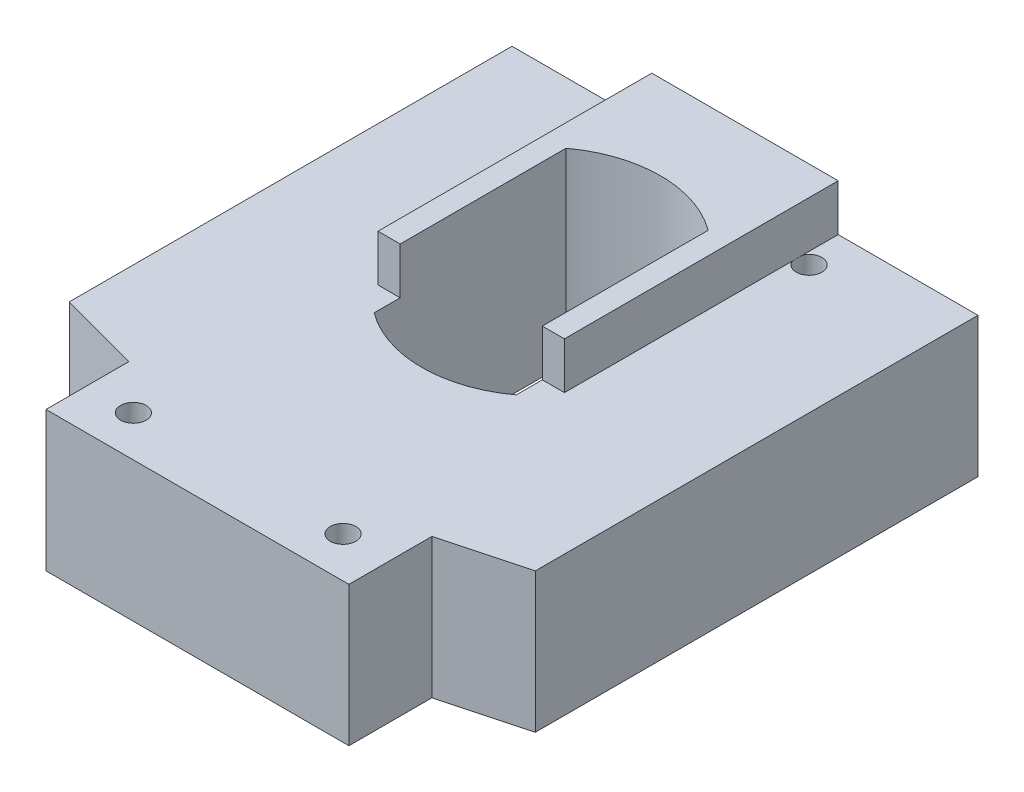
SolidWorks part; units mm, degrees
ref_plane "Front Plane" through (0, 0, 0) normal (0, 0, 1) x (1, 0, 0)
ref_plane "Top Plane" through (0, 0, 0) normal (0, 1, 0) x (1, 0, 0)
ref_plane "Right Plane" through (0, 0, 0) normal (1, 0, 0) x (0, 0, -1)
sketch "Sketch1" plane through (0, 0, 0) normal (0, 1, 0) x (1, 0, 0)
  line L0 (13, 23.5) -> (20, 23.5)
  line L1 (-9, -20) -> (9, -20) construction
  line L2 (-9, -20) -> (-9, 20) construction
  line L3 (-9, 20) -> (9, 20) construction
  line L4 (9, -20) -> (9, 20) construction
  line L5 (0, 20) -> (0, -20) construction
  line L6 (-9, 0) -> (9, 0) construction
  line L7 (-13, 23.5) -> (13, 23.5)
  line L8 (-13, 23.5) -> (-13, -23.5)
  line L9 (-13, -23.5) -> (13, -23.5)
  line L10 (13, 23.5) -> (13, -23.5)
  line L11 (0, -23.5) -> (0, 23.5) construction
  line L12 (-13, 0) -> (13, 0) construction
  line L13 (20, 23.5) -> (20, -14.5)
  line L14 (20, -14.5) -> (13, -16.3756)
  line L15 (-20, -14.5) -> (-13, -16.3756)
  line L16 (-20, 23.5) -> (-20, -14.5)
  line L17 (-13, 23.5) -> (-20, 23.5)
  circle A0 centre (-9, 20) radius 1.1
  circle A1 centre (9, 20) radius 1.1
  circle A2 centre (-9, -20) radius 1.1
  circle A3 centre (9, -20) radius 1.1
  point P0 (0, 0)
  point P8 (0, 0)
  point P18 (13, -16.7511)
  dimension "D3" = 2.2
  dimension "D1" = 18
  dimension "D2" = 40
  dimension "D4" = 26
  dimension "D5" = 47
  dimension "D6" = 38
  dimension "D7" = 40
  dimension "D8" = 75
extrude "Boss-Extrude1" add sketch "Sketch1" against normal blind 12 contours L8 L17 L16 L15 | L10 L7 L8 L9 A3 A2 A1 A0 | L14 L13 L0 L10 region at (0, 0, 0) region at (16.4719, 0, -4.0273) region at (-16.4719, 0, -4.0273)
sketch "Sketch2" plane through (0, 0, 0) normal (0, 0, 1) x (1, 0, 0)
  line L0 (0, -1000) -> (0, 49000) construction
  line L1 (-13, 0) -> (13, 0) construction
  line L2 (-8, 0) -> (-8, 4)
  line L3 (8, 0) -> (8, 4)
  line L4 (-8, 4) -> (8, 4)
  line L5 (-13, 0) -> (13, 0)
  circle A0 centre (-7, -4) radius 1.65
  circle A1 centre (7, -4) radius 1.65
  dimension "D1" = 3.3
  dimension "D2" = 14
  dimension "D3" = 4
  dimension "D4" = 16
  dimension "D5" = 4
extrude "Cut-Extrude1" [suppressed] cut sketch "Sketch2" against normal through all both and the other way through all contours A0 | A1
extrude "Boss-Extrude2" add sketch "Sketch2<3>" against normal up to surface (23.5 mm away) contours L0 L5 L3 L4 | L5 L0 L4 L2 region at (-4, 2, 0) region at (4, 2, 0) up to face at (0, -6, -23.5)
sketch "Sketch2<3>" plane through (0, 0, 0) normal (0, 0, 1) x (1, 0, 0) same geometry as "Sketch2"
sketch "Sketch3" plane through (0, 0, 0) normal (0, 1, 0) x (1, 0, 0)
  line L0 (20, 23.5) -> (-20, 23.5) construction
  line L1 (20, 23.5) -> (-20, 23.5) construction
  line L2 (0, -1000) -> (0, 49000) construction
  line L3 (-8, 0) -> (8, 0) construction
  line L4 (-1000, 6) -> (49000, 6) construction
  line L5 (-6.1, 14.2373) -> (-6.1, -2.2373)
  line L6 (6.1, 14.2373) -> (6.1, -2.2373)
  circle A0 centre (0, 6) radius 10.25
  point P10 (0, 0)
  dimension "D1" = 20.5
  dimension "D2" = 17.5
  dimension "D3" = 12.2
extrude "Cut-Extrude3" cut sketch "Sketch3" against normal through all both and the other way through all contours L6 A0 L5 region at (0, 0, -6)
